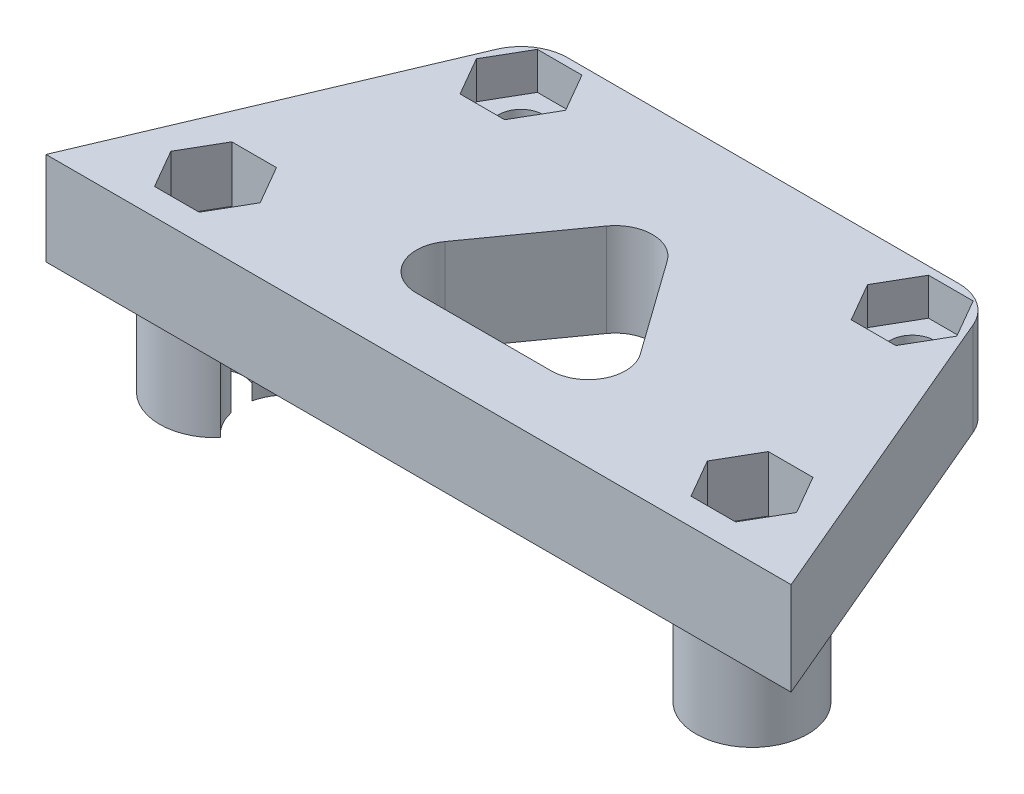
SolidWorks part; units mm, degrees
ref_plane "Front" through (0, 0, 0) normal (0, 0, 1) x (1, 0, 0)
ref_plane "Top" through (0, 0, 0) normal (0, 1, 0) x (1, 0, 0)
ref_plane "Right" through (0, 0, 0) normal (1, 0, 0) x (0, 0, -1)
sketch "Sketch1" plane through (0, 0, 0) normal (0, 1, 0) x (1, 0, 0)
  line L0 (-10.5, 0) -> (10.5, 0) construction
  line L5 (0, 0) -> (0, -2) construction
  line L6 (-10.5, 2.5) -> (10.5, 2.5)
  line L7 (-20, -16) -> (20, -16)
  line L8 (20, -16) -> (12.8016, 0.976)
  line L9 (-20, -16) -> (-12.8016, 0.976)
  line L10 (0, -2) -> (-7.5, -12.5)
  line L11 (-7.5, -12.5) -> (7.5, -12.5)
  line L12 (7.5, -12.5) -> (0, -2)
  circle A0 centre (-10.5, 0) radius 2.5
  circle A1 centre (10.5, 0) radius 2.5
  circle A2 centre (-14.4, -12.5) radius 1.5
  circle A3 centre (14.4, -12.5) radius 1.5
  point P5 (0, 0)
  point P11 (0, 0)
  point P12 (0, 0)
  point P16 (0, 0)
  dimension "D3" = 5
  dimension "D5" = 3
  dimension "D2" = 2
  dimension "D4" = 21
  dimension "D6" = 12.5
  dimension "D7" = 28.8
  dimension "D8" = 3.5
  dimension "D9" = 40
  dimension "D10" = 15
extrude "Boss-Extrude1" add sketch "Sketch1" along normal blind 5 contours A1 A0 | L12 L11 L10 L9 L7 L8 A3 A2 | A0 | A1 region at (0, 0, -2.0593)
hole_wizard "M2 Clearance Hole1" positions "Sketch2" profile "Sketch3" hole size "M2" standard "ANSI Metric" end condition through all
sketch "Sketch2" plane through (0, 5, 0) normal (0, 1, 0) x (1, 0, 0)
  point P5 (-10.5, 0)
  point P8 (10.5, 0)
  point P11 (-12.3019, 1.733)
  point P12 (0, 0)
sketch "Sketch3" plane through (-10.5, 5, 0) normal (1, 0, 0) x (0, 0, 1)
  line L0 (0, 0) -> (0, 5)
  line L1 (0, 5) -> (1.2, 5)
  line L2 (1.2, 5) -> (1.2, 0)
  line L5 (1.2, 0) -> (0, 0)
  line L11 (0, -6.35) -> (0, 107.95) construction
  dimension "Thru Hole Dia." = 2.4
  dimension "Thru Hole Depth" = 5
fillet "Fillet1" radius 2 3 edges at (7.5, 2.5, 12.5) (-7.5, 2.5, 12.5) (0, 2.5, 2)
sketch "Sketch4" plane through (0, 0, 0) normal (0, -1, 0) x (1, 0, 0)
  line L0 (11.8103, 10.2833) -> (-9.2279, -2.1521) construction
  line L1 (-11.7853, 2.1443) -> (9.1761, 14.7086) construction
  line L2 (0, -50) -> (0, 50) construction
  arc A0 (-12.8016, -0.976) -> (-10.5, -2.5) centre (-10.5, 0) ccw construction
  arc A1 (10.5, -2.5) -> (12.8016, -0.976) centre (10.5, 0) ccw construction
  arc A2 (-12.8016, -0.976) -> (-10.5, -2.5) centre (-10.5, 0) ccw
  arc A3 (10.5, -2.5) -> (12.8016, -0.976) centre (10.5, 0) ccw
  arc A4 (11.8103, 10.2833) -> (9.1761, 14.7086) centre (10.5, 12.5) ccw
  circle A5 centre (14.4, 12.5) radius 1.5 construction
  circle A6 centre (14.4, 12.5) radius 1.5
  circle A7 centre (-10.5, 0) radius 2.5 construction
  circle A8 centre (14.4, 12.5) radius 3
  arc A9 (9.1761, 14.7086) -> (11.8103, 10.2833) centre (10.5, 12.5) ccw construction
  circle A10 centre (-14.4, 12.5) radius 3
  arc A11 (-11.8103, 10.2833) -> (-9.1761, 14.7086) centre (-10.5, 12.5) cw
  circle M9 centre (14.4, 12.5) radius 1.5
  circle M10 centre (-14.4, 12.5) radius 1.5
  dimension "D1" = 5.15
  dimension "D2" = 6
extrude "Boss-Extrude2" add sketch "Sketch4" along normal blind 5 contours A4 A8 M9 | A10 A11 M10 region at (12.7636, 0, 11.1129) region at (-12.7636, 0, 13.8871)
sketch "Sketch5" plane through (0, 5, 0) normal (0, 1, 0) x (1, 0, 0)
  line L1 (13.202, -14.575) -> (15.598, -14.575)
  line L2 (15.598, -14.575) -> (16.796, -12.5)
  line L3 (16.796, -12.5) -> (15.598, -10.425)
  line L4 (15.598, -10.425) -> (13.202, -10.425)
  line L5 (13.202, -10.425) -> (12.004, -12.5)
  line L6 (12.004, -12.5) -> (13.202, -14.575)
  line L7 (-20, -16) -> (20, -16) construction
  line L8 (0, -50) -> (0, 50) construction
  line L9 (-12.004, -12.5) -> (-13.202, -14.575)
  line L10 (-13.202, -10.425) -> (-12.004, -12.5)
  line L11 (-15.598, -10.425) -> (-13.202, -10.425)
  line L12 (-16.796, -12.5) -> (-15.598, -10.425)
  line L13 (-15.598, -14.575) -> (-16.796, -12.5)
  line L14 (-13.202, -14.575) -> (-15.598, -14.575)
  circle A0 centre (14.4, -12.5) radius 1.5 construction
  circle A1 centre (14.4, -12.5) radius 1.5
  circle A2 centre (14.4, -12.5) radius 2.075 construction
  dimension "D1" = 4.15
extrude "Cut-Extrude1" cut sketch "Sketch5" against normal blind 3
sketch "Sketch6" plane through (0, 5, 0) normal (0, 1, 0) x (1, 0, 0)
  line L0 (-10.5, 2.5) -> (10.5, 2.5) construction
  line L1 (9.302, -2.075) -> (11.698, -2.075)
  line L2 (11.698, -2.075) -> (12.896, 0)
  line L3 (12.896, 0) -> (11.698, 2.075)
  line L4 (11.698, 2.075) -> (9.302, 2.075)
  line L5 (9.302, 2.075) -> (8.104, 0)
  line L6 (8.104, 0) -> (9.302, -2.075)
  line L7 (0, -50) -> (0, 50) construction
  line L9 (-8.104, 0) -> (-9.302, -2.075)
  line L10 (-9.302, 2.075) -> (-8.104, 0)
  line L11 (-11.698, 2.075) -> (-9.302, 2.075)
  line L12 (-12.896, 0) -> (-11.698, 2.075)
  line L13 (-11.698, -2.075) -> (-12.896, 0)
  line L14 (-9.302, -2.075) -> (-11.698, -2.075)
  circle A0 centre (10.5, 0) radius 1.2 construction
  circle A1 centre (10.5, 0) radius 1.2
  circle A2 centre (10.5, 0) radius 2.075 construction
  dimension "D1" = 4.15
extrude "Cut-Extrude2" cut sketch "Sketch6" against normal blind 2
